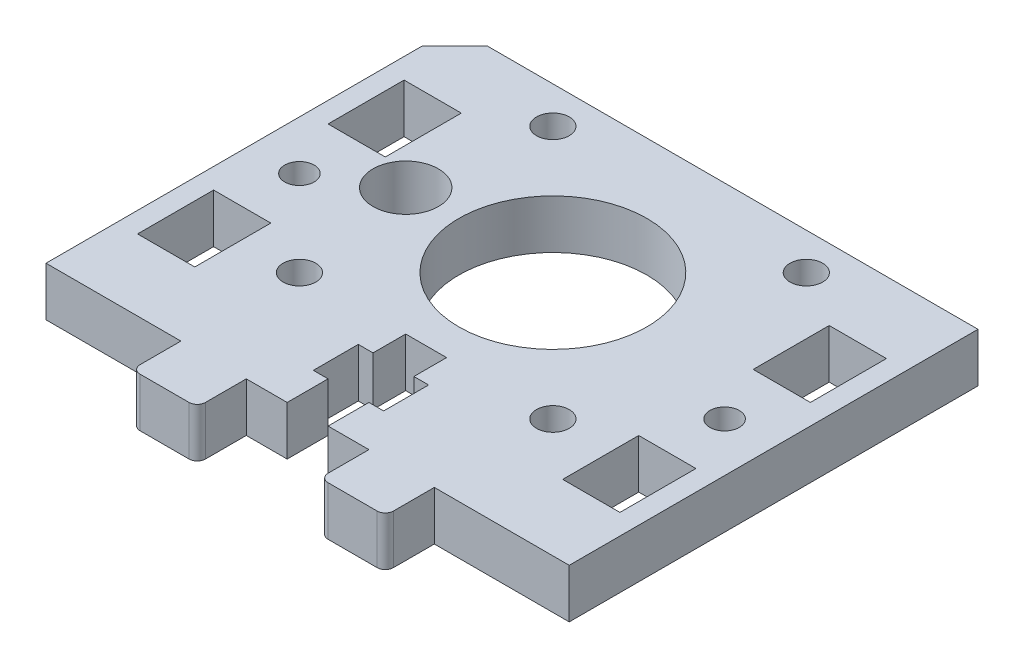
SolidWorks part; units mm, degrees
ref_plane "Plan de face" through (0, 0, 0) normal (0, 0, 1) x (1, 0, 0)
ref_plane "Plan de dessus" through (0, 0, 0) normal (0, 1, 0) x (1, 0, 0)
ref_plane "Plan de droite" through (0, 0, 0) normal (1, 0, 0) x (0, 0, -1)
sketch "Esquisse2" plane through (0, 0, 0) normal (0, 1, 0) x (1, 0, 0)
  line L0 (0, 25) -> (0, -25) construction
  line L1 (-32, -25) -> (32, -25)
  line L2 (-32, -25) -> (-32, 25)
  line L3 (-32, 25) -> (32, 25)
  line L4 (32, -25) -> (32, 25)
  line L5 (-32, -25) -> (32, 25) construction
  line L6 (-32, 25) -> (32, -25) construction
  line L7 (0, 5) -> (-32, 5) construction
  line L8 (26, 25) -> (26, -25) construction
  line L9 (-26, -25) -> (-26, 25) construction
  line L11 (-15.5, 20.5) -> (15.5, 20.5) construction
  line L12 (-15.5, 20.5) -> (-15.5, -10.5) construction
  line L13 (-15.5, -10.5) -> (15.5, -10.5) construction
  line L14 (15.5, 20.5) -> (15.5, -10.5) construction
  line L15 (-15.5, 20.5) -> (15.5, -10.5) construction
  line L16 (-15.5, -10.5) -> (15.5, 20.5) construction
  circle A0 centre (0, 5) radius 11.5
  circle A1 centre (-18, 5) radius 4
  circle A2 centre (15.5, -10.5) radius 2
  circle A3 centre (15.5, 20.5) radius 2
  circle A4 centre (-15.5, 20.5) radius 2
  circle A5 centre (-15.5, -10.5) radius 2
  point P0 (0, 0)
  line B0 (29.5, 16.3) -> (29.5, 7)
  line B1 (29.5, 16.3) -> (22.5, 16.3)
  line B2 (22.5, 16.3) -> (22.5, 7)
  line B3 (29.5, 7) -> (22.5, 7)
  line B4 (29.5, -7) -> (22.5, -7)
  line B5 (22.5, -16.3) -> (22.5, -7)
  line B6 (29.5, -16.3) -> (22.5, -16.3)
  line B7 (29.5, -16.3) -> (29.5, -7)
  circle B8 centre (26, 0) radius 1.8
  line B9 (-29.5, -16.3) -> (-29.5, -7)
  line B10 (-29.5, -16.3) -> (-22.5, -16.3)
  line B11 (-22.5, -16.3) -> (-22.5, -7)
  line B12 (-29.5, -7) -> (-22.5, -7)
  line B13 (-29.5, 7) -> (-22.5, 7)
  line B14 (-22.5, 16.3) -> (-22.5, 7)
  line B15 (-29.5, 16.3) -> (-22.5, 16.3)
  line B16 (-29.5, 16.3) -> (-29.5, 7)
  circle B17 centre (-26, 0) radius 1.8
  dimension "D4" = 23
  dimension "D5" = 8
  dimension "D9" = 4
  dimension "D1" = 64
  dimension "D2" = 50
  dimension "D3" = 20
  dimension "D6" = 14
  dimension "D7" = 6
  dimension "D8" = 6
  dimension "D10" = 31
sketch_block_instance "Bloc-attache-femelle-1"
sketch_block "Bloc-attache-femelle" parameters "D1"=3.6, "D2"=9.3, "D3"=7, "D4"=7
sketch_block_instance "Bloc-attache-femelle-2"
extrude "Boss.-Extru.1" add sketch "Esquisse2" along normal mid plane 6
sketch "Esquisse3" plane through (0, 3, 0) normal (0, 1, 0) x (1, 0, 0)
  line L0 (-32, -25) -> (32, -25) construction
  line B0 (15.5, -25) -> (15.5, -30)
  line B1 (14.5, -31) -> (8.5, -31)
  line B2 (7.5, -30) -> (7.5, -25)
  line B3 (7.5, -25) -> (2.5, -25)
  line B4 (2.5, -25) -> (2.5, -20)
  line B5 (2.5, -20) -> (4.3, -20)
  line B6 (4.3, -20) -> (4.3, -14.5)
  line B7 (4.3, -14.5) -> (2.5, -14.5)
  line B8 (2.5, -14.5) -> (2.5, -10.5)
  line B9 (2.5, -10.5) -> (-2.5, -10.5)
  line B10 (0, -10.5) -> (0, -25) construction
  line B11 (-15.5, -25) -> (-7.5, -25)
  line B12 (7.5, -25) -> (15.5, -25)
  line B13 (-2.5, -14.5) -> (-2.5, -10.5)
  line B14 (-4.3, -14.5) -> (-2.5, -14.5)
  line B15 (-4.3, -20) -> (-4.3, -14.5)
  line B16 (-2.5, -20) -> (-4.3, -20)
  line B17 (-2.5, -25) -> (-2.5, -20)
  line B18 (-7.5, -25) -> (-2.5, -25)
  line B19 (-7.5, -30) -> (-7.5, -25)
  line B20 (-14.5, -31) -> (-8.5, -31)
  line B21 (-15.5, -25) -> (-15.5, -30)
  line B22 (2.5, -25) -> (-2.5, -25)
  arc B23 (8.5, -31) -> (7.5, -30) centre (8.5, -30) cw
  arc B24 (15.5, -30) -> (14.5, -31) centre (14.5, -30) cw
  arc B25 (-15.5, -30) -> (-14.5, -31) centre (-14.5, -30) ccw
  arc B26 (-8.5, -31) -> (-7.5, -30) centre (-8.5, -30) ccw
  line M14 (-32, -25) -> (32, -25)
sketch_block_instance "Bloc-attache-male-1"
sketch_block "Bloc-attache-male" parameters "D7"=1, "D1"=5, "D2"=5, "D3"=5.5, "D4"=1.8, "D5"=4, "D6"=2.5
extrude "Boss.-Extru.2" add sketch "Esquisse3" against normal blind 6 contours B20 B26 B19 B21 B25 M14 | B24 B0 B2 B23 B1 M14 region at (-11.5, 3, 27.9749) region at (11.5, 3, 27.9749)
extrude "Enlèv. mat.-Extru.1" cut sketch "Esquisse3<3>" against normal blind 6 contours B17 B4 B5 B6 B7 B8 B9 B13 B14 B15 B16 M14 region at (0, 3, 17.6427)
sketch "Esquisse3<3>" plane through (0, 3, 0) normal (0, 1, 0) x (1, 0, 0) same geometry as "Esquisse3"
chamfer "Chanfrein1" distance 4 angle 45 1 edges at (-32, 0, -25)
